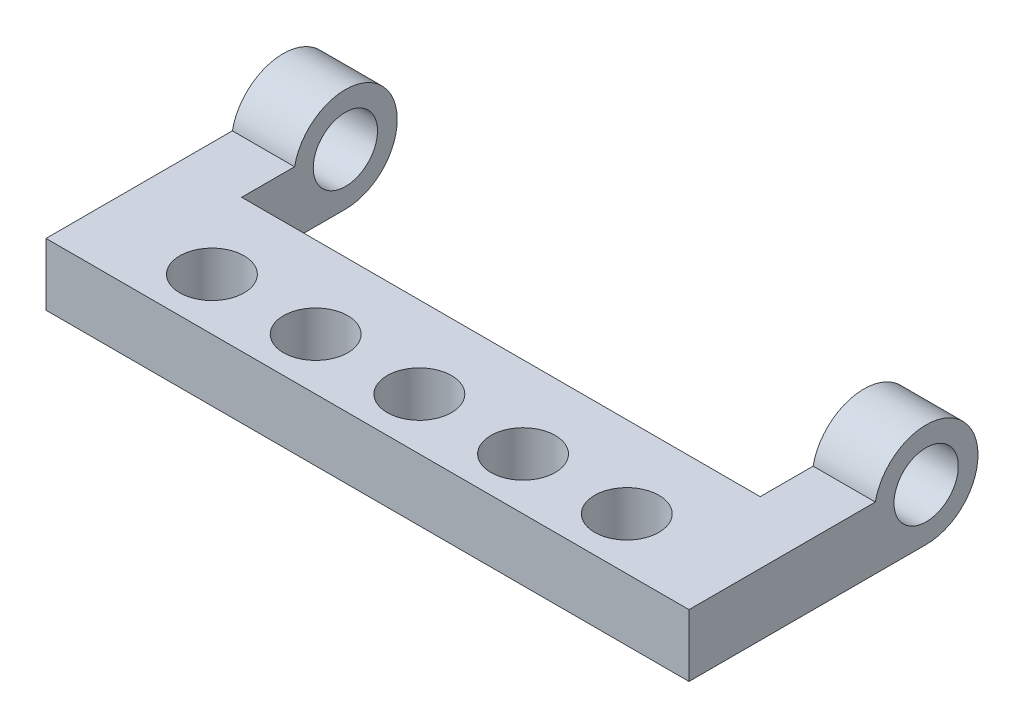
SolidWorks part; units mm, degrees
ref_plane "Front Plane" through (0, 0, 0) normal (0, 0, 1) x (1, 0, 0)
ref_plane "Top Plane" through (0, 0, 0) normal (0, 1, 0) x (1, 0, 0)
ref_plane "Right Plane" through (0, 0, 0) normal (1, 0, 0) x (0, 0, -1)
sketch "Sketch1" plane through (0, 0, 0) normal (0, 1, 0) x (1, 0, 0)
  line L0 (0, -55) -> (0, 55) construction
  line L1 (-15.5, 5.7164) -> (15.5, 5.7164)
  line L2 (-15.5, 5.7164) -> (-15.5, -5.7164)
  line L3 (-15.5, -5.7164) -> (15.5, -5.7164)
  line L4 (15.5, 5.7164) -> (15.5, -5.7164)
  line L5 (-15.5, 5.7164) -> (15.5, -5.7164) construction
  line L6 (-15.5, -5.7164) -> (15.5, 5.7164) construction
  circle A0 centre (0, -3.2164) radius 1.55
  circle A1 centre (5, -3.2164) radius 1.55
  circle A2 centre (10, -3.2164) radius 1.55
  circle A3 centre (-5, -3.2164) radius 1.55
  circle A4 centre (-10, -3.2164) radius 1.55
  point P0 (0, 0)
  dimension "D2" = 3.1
  dimension "D1" = 31
  dimension "D3" = 2.5
  dimension "D4" = 3
  dimension "D5" = 3
extrude "Boss-Extrude1" add sketch "Sketch1" along normal blind 3
sketch "Sketch2" plane through (-15.5, 0, 0) normal (-1, 0, 0) x (0, 0, 1)
  line L0 (6.2881, 0) -> (-6.2881, 0) construction
  circle A0 centre (-5.7164, 2.5) radius 1.55
  circle A1 centre (-5.7164, 2.5) radius 2.5
  dimension "D1" = 5
  dimension "D2" = 2.5
  dimension "D3" = 3.1
extrude "Cut-Extrude1" cut sketch "Sketch2" against normal up to surface (31 mm away) contours A0 up to face at (15.5, 1.5, 0)
extrude "Boss-Extrude2" add sketch "Sketch2<3>" against normal up to surface (31 mm away) up to face at (15.5, 1.3146, -0.7445)
sketch "Sketch2<3>" plane through (-15.5, 0, 0) normal (-1, 0, 0) x (0, 0, 1) same geometry as "Sketch2"
sketch "Sketch3" plane through (0, 0, 0) normal (0, -1, 0) x (1, 0, 0)
  line L0 (0, -2.75) -> (0, 2.75) construction
  line L1 (15.5, -5.7164) -> (-15.5, -5.7164) construction
  line L2 (-12.5, -0.7164) -> (12.5, -0.7164)
  line L3 (-12.5, -0.7164) -> (-12.5, -8.2164)
  line L4 (-12.5, -8.2164) -> (12.5, -8.2164)
  line L5 (12.5, -0.7164) -> (12.5, -8.2164)
  line L6 (-12.5, -0.7164) -> (12.5, -8.2164) construction
  line L7 (-12.5, -8.2164) -> (12.5, -0.7164) construction
  line L8 (-15.5, -8.2164) -> (15.5, -8.2164) construction
  point P2 (0, -4.4664)
  dimension "D1" = 25
  dimension "D2" = 5
extrude "Cut-Extrude2" cut sketch "Sketch3" against normal through all
